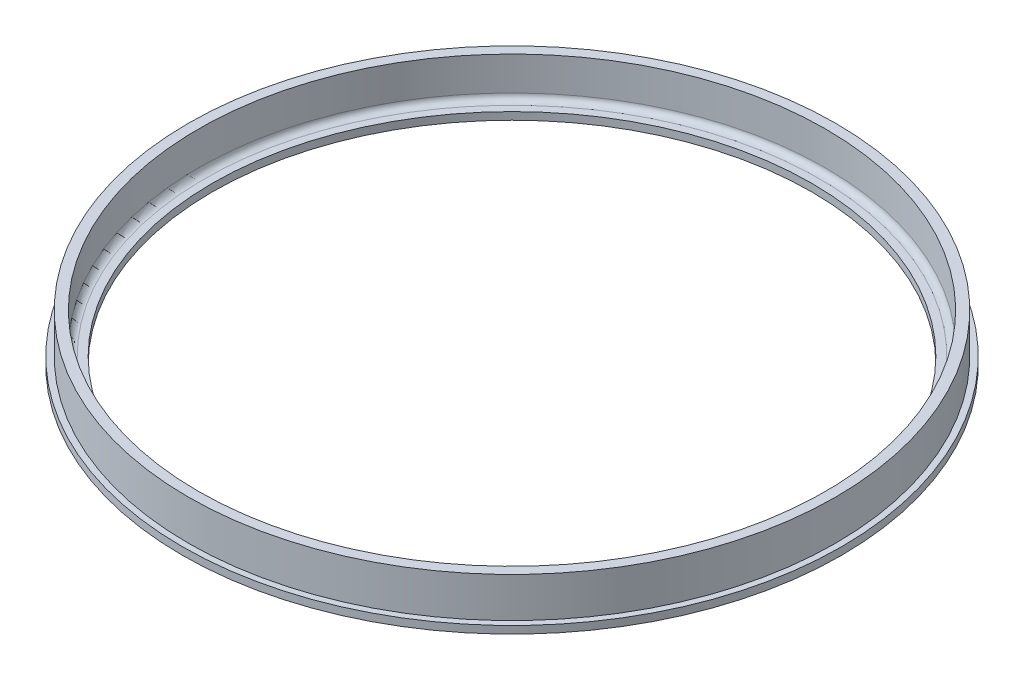
SolidWorks part; units mm, degrees
material "6061-T6 (SS)"
ref_plane "Front" through (0, 0, 0) normal (0, 0, 1) x (1, 0, 0)
ref_plane "Top" through (0, 0, 0) normal (0, 1, 0) x (1, 0, 0)
ref_plane "Right" through (0, 0, 0) normal (1, 0, 0) x (0, 0, -1)
sketch "Sketch1" plane through (0, 0, 0) normal (0, 0, 1) x (1, 0, 0)
  line L0 (0, 0) -> (0, 35.9551) construction
  line L1 (-83.82, -19.3305) -> (-83.82, -17.4255)
  line L2 (-83.82, -17.4255) -> (-82.296, -17.4255)
  line L3 (-76.2, -7.2655) -> (-76.2, -17.4255)
  line L4 (-82.296, -17.4255) -> (-82.296, -7.2655)
  line L5 (-76.2, -17.4255) -> (-76.2, -19.3305)
  line L6 (-76.2, -19.3305) -> (-83.82, -19.3305)
  line L7 (-76.2, -7.2655) -> (-82.296, -7.2655)
  dimension "D1" = 76.2
  dimension "D2" = 1.524
  dimension "D3" = 1.905
  dimension "D4" = 10.16
  dimension "D5" = 83.82
revolve "Revolve1" add sketch "Sketch1" angle 360 about L0
sketch "Sketch2" plane through (0, -7.2655, 0) normal (0, 1, 0) x (1, 0, 0)
  circle A0 centre (0, 0) radius 79.756
  circle A1 centre (0, 0) radius 82.296 construction
  circle A2 centre (0, 0) radius 82.296
  circle M2 centre (0, 0) radius 76.2
  dimension "D1" = 2.54
extrude "Cut-Extrude1" cut sketch "Sketch2" against normal blind 10.16 contours A0 M2 region at (-77.5002, -7.2655, 0)
fillet "Fillet1" radius 1.5875 1 edges at (0, -17.4255, 79.756)
